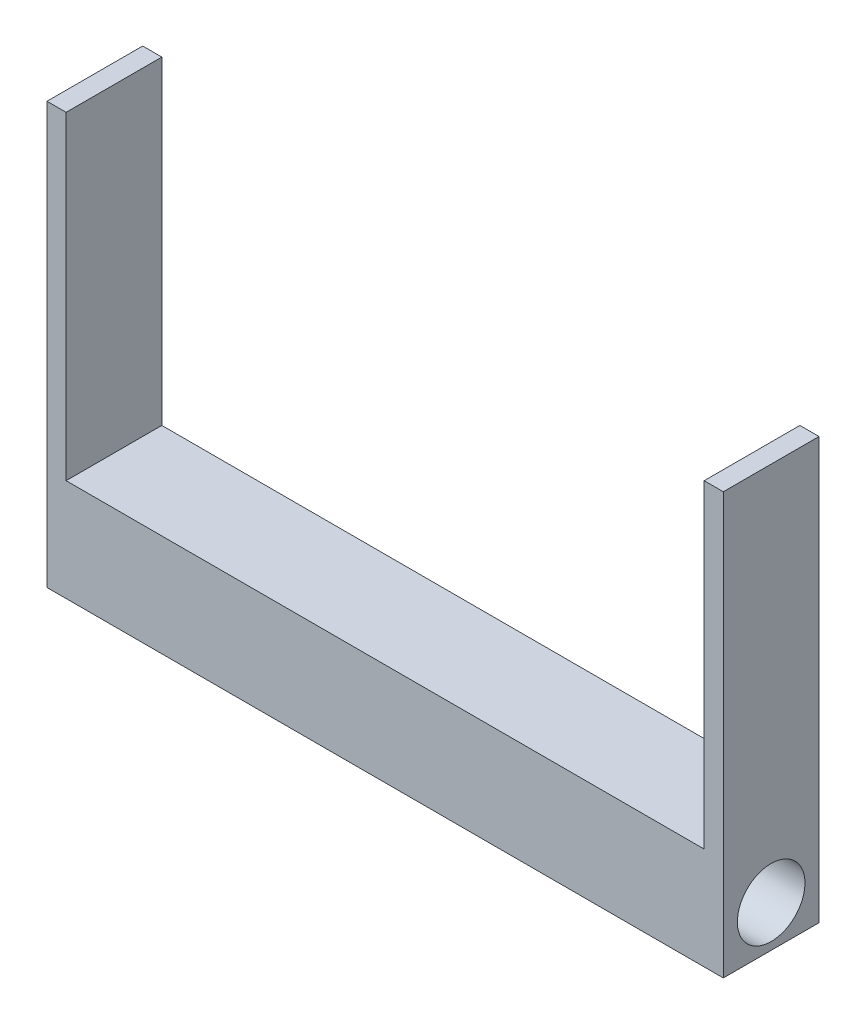
SolidWorks part; units mm, degrees
material "PLA"
ref_plane "Front Plane" through (0, 0, 0) normal (0, 0, 1) x (1, 0, 0)
ref_plane "Top Plane" through (0, 0, 0) normal (0, 1, 0) x (1, 0, 0)
ref_plane "Right Plane" through (0, 0, 0) normal (1, 0, 0) x (0, 0, -1)
sketch "Sketch1" plane through (0, 0, 0) normal (0, 0, 1) x (1, 0, 0)
  line L0 (-50, 0) -> (-50, -50)
  line L1 (-50, -50) -> (50, -50)
  line L2 (50, -50) -> (50, 0)
  dimension "D1" = 50
  dimension "D2" = 100
  dimension "D3" = 50
  dimension "D4" = 50
extrude "Extrude-Thin1" add sketch "Sketch1" along normal mid plane 15 thin thin type one direction wall 3
sketch "Sketch4" plane through (0, -53, 0) normal (0, -1, 0) x (1, 0, 0)
  line L4 (-53, -7.5) -> (53, -7.5)
  line L5 (53, -7.5) -> (53, 7.5)
  line L6 (53, 7.5) -> (-53, 7.5)
  line L7 (-53, 7.5) -> (-53, -7.5)
  line L8 (-53, -7.5) -> (53, -7.5)
  line L9 (53, -7.5) -> (53, 7.5)
  line L10 (53, 7.5) -> (-53, 7.5)
  line L11 (-53, 7.5) -> (-53, -7.5)
  dimension "D1" = 0
extrude "Boss-Extrude1" add sketch "Sketch4" along normal blind 13
sketch "Sketch5" plane through (53, 0, 0) normal (1, 0, 0) x (0, 0, -1)
  line L0 (7.5, -66) -> (-7.5, -66) construction
  line L1 (-7.5, -66) -> (-7.5, 0) construction
  circle A0 centre (0, -59.5) radius 5.3
  dimension "D1" = 10.6
  dimension "D2" = 6.5
  dimension "D3" = 7.5
extrude "Cut-Extrude1" cut sketch "Sketch5" against normal through all
